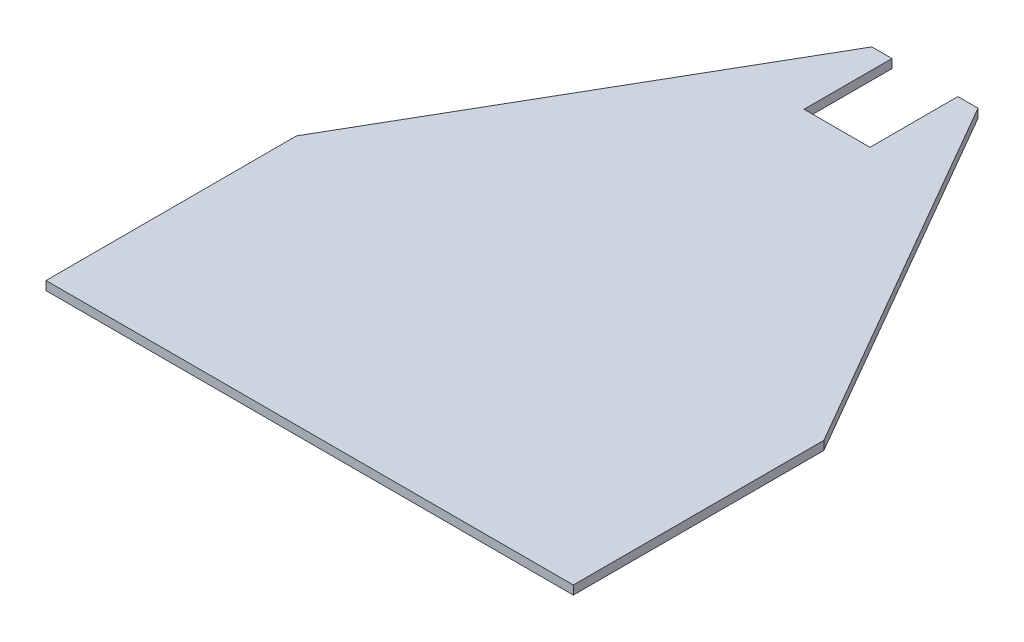
SolidWorks part; units mm, degrees
material "1.0116 (S235J2G3)"
ref_plane "Front Plane" through (0, 0, 0) normal (0, 0, 1) x (1, 0, 0)
ref_plane "Top Plane" through (0, 0, 0) normal (0, 1, 0) x (1, 0, 0)
ref_plane "Right Plane" through (0, 0, 0) normal (1, 0, 0) x (0, 0, -1)
sketch "Sketch1" plane through (0, 0, 0) normal (0, 1, 0) x (1, 0, 0)
  line L0 (0, 0) -> (0, 1800) construction
  line L1 (600, 0) -> (-600, 0)
  line L2 (-600, 0) -> (-600, 570)
  line L3 (-600, 570) -> (-120.7993, 1400)
  line L4 (-120.7993, 1400) -> (-75, 1400)
  line L5 (-75, 1400) -> (-75, 1200)
  line L6 (-75, 1200) -> (75, 1200)
  line L7 (75, 1400) -> (75, 1200)
  line L8 (120.7993, 1400) -> (75, 1400)
  line L9 (600, 570) -> (120.7993, 1400)
  line L10 (600, 0) -> (600, 570)
  point P3 (-97.8996, 1400)
  point P11 (0, 1200)
  dimension "D1" = 1800
  dimension "D2" = 600
  dimension "D3" = 570
  dimension "D4" = 1400
  dimension "D5" = 75
  dimension "D6" = 60
  dimension "D7" = 200
extrude "Boss-Extrude2" add sketch "Sketch1" along normal blind 20
